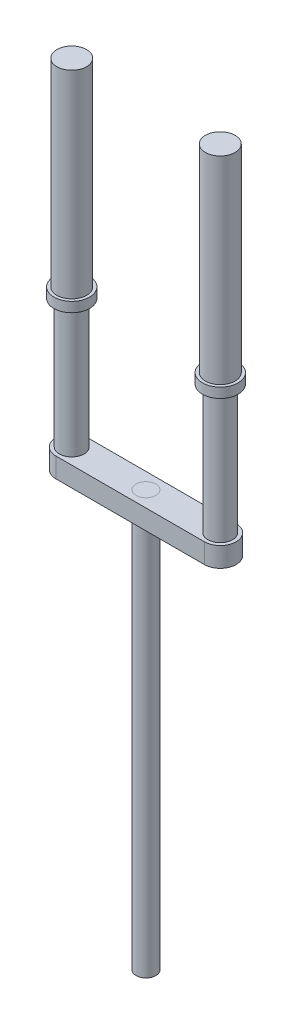
SolidWorks part; units mm, degrees
material "Chrome Stainless Steel"
ref_plane "Front Plane" through (0, 0, 0) normal (0, 0, 1) x (1, 0, 0)
ref_plane "Top Plane" through (0, 0, 0) normal (0, 1, 0) x (1, 0, 0)
ref_plane "Right Plane" through (0, 0, 0) normal (1, 0, 0) x (0, 0, -1)
sketch "Sketch1" plane through (0, 0, 0) normal (0, 1, 0) x (1, 0, 0)
  line L1 (-75, 16) -> (75, 16)
  line L2 (-75, -16) -> (75, -16)
  circle A0 centre (0, 0) radius 10
  circle A1 centre (75, 0) radius 12.5
  arc A2 (75, -16) -> (75, 16) centre (75, 0) ccw
  arc A3 (-75, -16) -> (-75, 16) centre (-75, 0) cw
  circle A4 centre (-75, 0) radius 12.5
  point P5 (0, 0)
  point P8 (0, 0)
extrude "Boss-Extrude1" add sketch "Sketch1" along normal blind 20
extrude "Boss-Extrude2" add sketch "Sketch1<3>" against normal blind 400 and the other way blind 20 separate body contours A0
sketch "Sketch1<3>" plane through (0, 0, 0) normal (0, 1, 0) x (1, 0, 0) same geometry as "Sketch1"
extrude "Boss-Extrude3" add sketch "Sketch1<5>" along normal blind 360 contours A4 | A1 region at (75, 0, 0) region at (-75, 0, 0)
sketch "Sketch1<5>" plane through (0, 0, 0) normal (0, 1, 0) x (1, 0, 0) same geometry as "Sketch1"
sketch "Sketch3" plane through (0, 360, 0) normal (0, 1, 0) x (1, 0, 0)
  line L0 (0, 0) -> (75, 0)
  line L1 (0, 0) -> (0, 63.6051)
  circle A0 centre (75, 0) radius 15
  circle A1 centre (-75, 0) radius 15
extrude "Boss-Extrude4" add sketch "Sketch3" against normal blind 200 contours A1 | A0 region at (-75, 360, 0)
sketch "Sketch4" plane through (0, 160, 0) normal (0, -1, 0) x (1, 0, 0)
  circle A0 centre (-75, 0) radius 18
  circle A1 centre (75, 0) radius 18
extrude "Boss-Extrude5" add sketch "Sketch4" along normal blind 10
